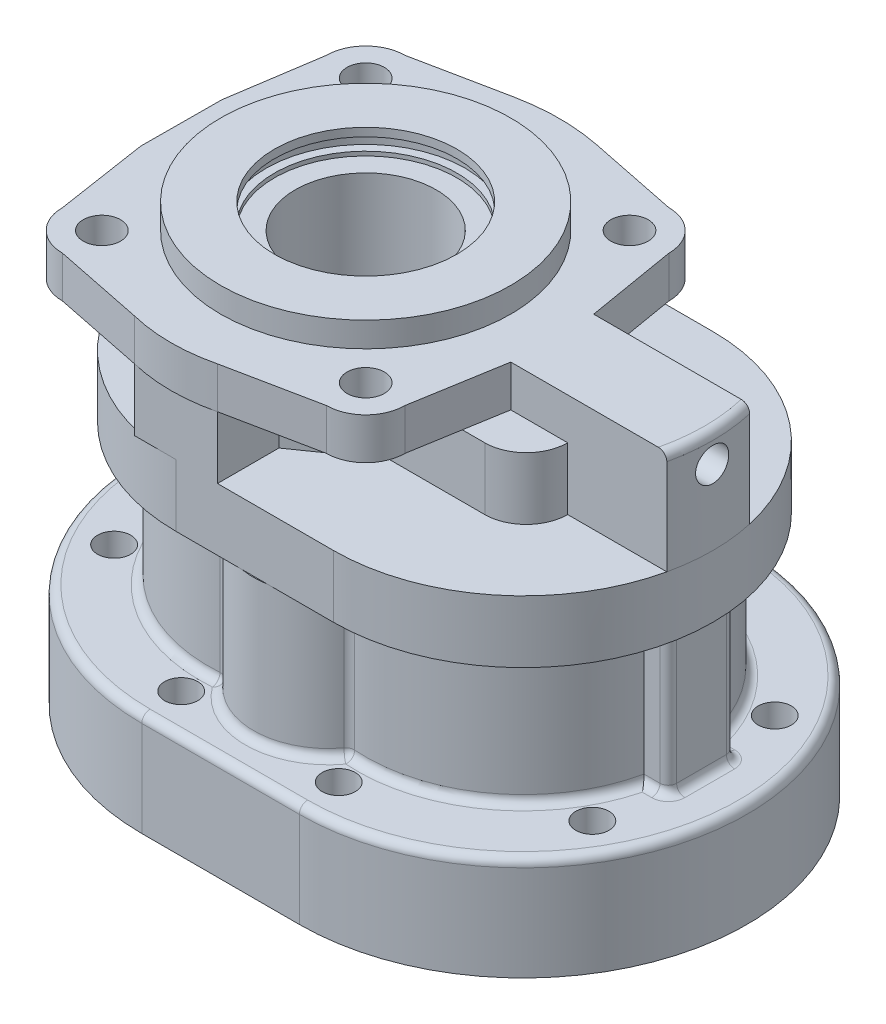
SolidWorks part; units mm, degrees
material "1.4000 (X6Cr13)"
ref_plane "Спереди" through (0, 0, 0) normal (0, 0, 1) x (1, 0, 0)
ref_plane "Сверху" through (0, 0, 0) normal (0, 1, 0) x (1, 0, 0)
ref_plane "Справа" through (0, 0, 0) normal (1, 0, 0) x (0, 0, -1)
sketch "Эскиз2" plane through (0, 0, 0) normal (0, 1, 0) x (1, 0, 0)
  line L0 (-87.7274, 0) -> (85.7597, 0) construction
  line L1 (6.0246, 54) -> (-31.9754, 54)
  line L2 (6.0246, -54) -> (-31.9754, -54)
  arc A3 (-31.9754, 54) -> (-31.9754, -54) centre (-31.9754, 0) ccw
  arc A4 (6.0246, -54) -> (6.0246, 54) centre (6.0246, 0) ccw
  dimension "D5" = 108
  dimension "D1" = 38
extrude "Вытянуть2" add sketch "Эскиз2" along normal blind 25
sketch "Эскиз4" plane through (0, 25, 0) normal (0, 1, 0) x (1, 0, 0)
  line L0 (91.9674, 0) -> (-114.468, 0) construction
  circle A8 centre (44.706, 22) radius 4
  circle A9 centre (44.706, -22) radius 4
  circle A10 centre (-70.6568, -22) radius 4
  circle A11 centre (-70.6568, 22) radius 4
  circle A12 centre (-31.9754, -44.5) radius 4
  circle A13 centre (6.0246, -44.5) radius 4
  circle A14 centre (6.0246, 44.5) radius 4
  circle A15 centre (-31.9754, 44.5) radius 4
  dimension "D6" = 8
  dimension "D7" = 8
  dimension "D8" = 8
  dimension "D9" = 8
  dimension "D10" = 8
  dimension "D11" = 8
  dimension "D12" = 8
  dimension "D13" = 8
extrude "Вырез-Вытянуть2" cut sketch "Эскиз4" against normal through all
sketch "Эскиз5" plane through (0, 25, 0) normal (0, 1, 0) x (1, 0, 0)
  line L0 (70.9678, 0) -> (-102.4067, 0) construction
  line L1 (6.0246, 38) -> (2.0064, 38)
  line L2 (-31.9754, -38) -> (-27.9572, -38)
  line L3 (2.0064, -38) -> (6.0246, -38)
  line L4 (-27.9572, 38) -> (-31.9754, 38)
  line L5 (-69.9754, 0) -> (-80.9754, 0)
  line L6 (44.0246, 0) -> (55.0246, 0)
  arc A1 (-28.0881, 37.8006) -> (-28.0881, -37.8006) centre (-31.9754, 0) ccw
  arc A2 (2.1373, 37.8006) -> (-28.0881, 37.8006) centre (-12.9754, 28.0227) ccw
  arc A3 (-26.574, -16.2296) -> (-27.6526, -17.6025) centre (-12.9754, -28.0227) ccw
  arc A4 (-28.0881, -37.8006) -> (2.1373, -37.8006) centre (-12.9754, -28.0227) ccw
  arc A5 (0.6232, 16.2296) -> (1.7018, 17.6025) centre (-12.9754, 28.0227) ccw
  arc A7 (2.1373, -37.8006) -> (2.1373, 37.8006) centre (6.0246, 0) ccw
  dimension "D1" = 76
  dimension "D3" = 36
extrude "Вытянуть5" add sketch "Эскиз5" along normal blind 34 contours L0 A7 A2 A1 | A7 L0 A1 A4 region at (-12.9754, 25, 18.2894) region at (-12.9754, 25, -18.2894)
sketch "Эскиз7" plane through (0, 25, 0) normal (0, 1, 0) x (1, 0, 0)
  line L1 (33.7864, 8) -> (33.7864, -8)
  line L3 (49.0246, 8) -> (49.0246, -8)
  line L4 (-12.9754, 63.0794) -> (-12.9754, -64.61) construction
  line L5 (49.0246, 8) -> (33.7864, 8)
  line L6 (49.0246, -8) -> (33.7864, -8)
  line L9 (-59.7372, 8) -> (-59.7372, -8)
  line L10 (6.0246, 0) -> (-93.5345, 0) construction
  line L11 (-74.9754, -8) -> (-59.7372, -8)
  line L12 (-74.9754, 8) -> (-74.9754, -8)
  line L13 (-74.9754, 8) -> (-59.7372, 8)
extrude "Вытянуть6" add sketch "Эскиз7" along normal blind 34
sketch "Эскиз9" plane through (0, 59, 0) normal (0, 1, 0) x (1, 0, 0)
  line L0 (77.4288, 0) -> (-110.5641, 0) construction
  line L1 (-110.5641, 0) -> (-110.2647, -0.7484) construction
  line L2 (-12.9754, 54) -> (-12.9754, 79.7772) construction
  line L3 (6.0246, 54) -> (-31.9754, 54) construction
  line L4 (-12.9754, 79.7772) -> (-12.9754, 45.75) construction
  line L5 (6.0246, 45.75) -> (-31.9754, 45.75)
  line L6 (6.0246, -45.75) -> (-31.9754, -45.75)
  line L7 (-12.9754, -45.75) -> (-12.9754, -73.7902) construction
  arc A0 (6.0246, -45.75) -> (6.0246, 45.75) centre (6.0246, 0) ccw
  arc A1 (-31.9754, 45.75) -> (-31.9754, -45.75) centre (-31.9754, 0) ccw
  dimension "D1" = 91.5
  dimension "D2" = 91.5
extrude "Вытянуть8" add sketch "Эскиз9" along normal blind 15
sketch "Эскиз10" plane through (0, 74, 0) normal (0, 1, 0) x (1, 0, 0)
  line L0 (73.3377, 0) -> (-104.2777, 0) construction
  line L1 (-31.9754, 59.8254) -> (-31.9754, -62.6925) construction
  line L2 (-21.9754, 45.75) -> (-41.9754, 45.75)
  line L3 (6.0246, 45.75) -> (-31.9754, 45.75) construction
  line L4 (-21.9754, 45.75) -> (-21.9754, 30.9233)
  line L5 (-31.9754, -45.75) -> (6.0246, -45.75) construction
  line L6 (-21.9754, -45.75) -> (-41.9754, -45.75)
  line L7 (-41.9754, 45.75) -> (-41.9754, 30.9233)
  line L8 (-76.6191, 10) -> (-76.6191, -10)
  line L9 (-76.6191, -10) -> (-62.8987, -10)
  line L10 (26.7556, 20) -> (26.7556, -20)
  line L11 (26.7556, 20) -> (-6.358, 20)
  line L12 (-6.358, 20) -> (-21.9754, 30.9233)
  line L13 (-41.9754, -30.9233) -> (-41.9754, -45.75)
  line L14 (-62.8987, 10) -> (-76.6191, 10)
  line L15 (-6.358, -20) -> (26.7556, -20)
  line L16 (-21.9754, -30.9233) -> (-21.9754, -45.75)
  line L17 (-6.358, -20) -> (-21.9754, -30.9233)
  arc A0 (-41.9754, 30.9233) -> (-62.8987, 10) centre (-31.9754, 0) ccw
  arc A1 (-31.9754, 45.75) -> (-31.9754, -45.75) centre (-31.9754, 0) ccw construction
  arc A3 (-62.8987, -10) -> (-41.9754, -30.9233) centre (-31.9754, 0) ccw
  point P19 (-31.9754, 45.75)
  point P20 (-31.9754, -45.75)
  point P29 (26.7556, 0)
  dimension "D1" = 65
  dimension "D2" = 20
extrude "Вытянуть12" add sketch "Эскиз10" along normal blind 15
sketch "Эскиз11" plane through (0, 89, 0) normal (0, 1, 0) x (1, 0, 0)
  line L0 (-91.5552, 0) -> (46.0634, 0) construction
  line L2 (-31.9754, -57.3023) -> (-31.9754, 59.4606) construction
  line L3 (13.0246, -10) -> (13.0246, 10)
  line L4 (13.0246, 10) -> (9.3444, 31.8198)
  line L5 (-0.1556, 41.3198) -> (-21.9754, 45.75)
  line L6 (-41.9754, 45.75) -> (-63.7952, 41.3198)
  line L7 (-73.2952, 31.8198) -> (-76.6191, 10)
  line L8 (-76.6191, 10) -> (-76.7193, -9.5419)
  line L9 (-76.7193, -9.5419) -> (-73.2952, -31.8198)
  line L10 (13.0246, -10) -> (9.3444, -31.8198)
  line L11 (-0.1556, -41.3198) -> (-21.9754, -45.75)
  line L12 (-63.7952, -41.3198) -> (-41.9754, -45.75)
  arc A1 (9.3444, 31.8198) -> (-0.1556, 41.3198) centre (-0.1556, 31.8198) ccw
  arc A2 (-21.9754, 45.75) -> (-41.9754, 45.75) centre (-31.9754, -3.5025) ccw
  arc A3 (-73.2952, 31.8198) -> (-63.7952, 41.3198) centre (-63.7952, 31.8198) cw
  arc A4 (-73.2952, -31.8198) -> (-63.7952, -41.3198) centre (-63.7952, -31.8198) ccw
  arc A5 (9.3444, -31.8198) -> (-0.1556, -41.3198) centre (-0.1556, -31.8198) cw
  arc A6 (-76.6191, 10) -> (-76.6191, -10) centre (-31.9754, 0) ccw construction
  arc A7 (-41.9754, -45.75) -> (-21.9754, -45.75) centre (-31.9754, -4.7961) ccw
  point P13 (13.0246, 0)
  dimension "D1" = 19
  dimension "D2" = 10
extrude "Вытянуть14" add sketch "Эскиз11" along normal blind 10
sketch "Эскиз12" plane through (0, 74, 0) normal (0, 1, 0) x (1, 0, 0)
  line L0 (19.9545, 0) -> (78.4595, 0) construction
  line L2 (50.6683, 10) -> (13.0246, 10)
  line L3 (13.0246, 10) -> (13.0246, -10)
  line L4 (13.0246, -10) -> (50.6683, -10)
  arc A0 (6.0246, -45.75) -> (6.0246, 45.75) centre (6.0246, 0) ccw construction
  arc A1 (50.6683, 10) -> (50.6683, -10) centre (6.3738, 0) cw
  point P9 (50.6683, 0)
  dimension "D1" = 10
extrude "Вытянуть15" add sketch "Эскиз12" along normal blind 25
fillet "Скругление12" radius 10 1 edges at (26.7556, 81.5, 20)
fillet "Скругление13" radius 10 1 edges at (26.7556, 81.5, -20)
sketch "Эскиз13" plane through (0, 0, 0) normal (0, -1, 0) x (1, 0, 0)
  line L0 (66.2281, 0) -> (-91.7631, 0) construction
  circle A0 centre (6.0246, 0) radius 22
extrude "Вырез-Вытянуть5" cut sketch "Эскиз13" against normal blind 68
sketch "Эскиз14" plane through (0, 68, 0) normal (0, -1, 0) x (1, 0, 0)
  circle A0 centre (6.0246, 0) radius 11.5
  dimension "D1" = 23
extrude "Вырез-Вытянуть6" cut sketch "Эскиз14" against normal blind 10
sketch "Эскиз15" plane through (0, 0, 0) normal (0, -1, 0) x (1, 0, 0)
  line L0 (68.4793, 0) -> (-98.8794, 0) construction
  circle A0 centre (-31.9754, 0) radius 22
  dimension "D1" = 44
extrude "Вырез-Вытянуть7" cut sketch "Эскиз15" against normal blind 68
sketch "Эскиз16" plane through (0, 68, 0) normal (0, -1, 0) x (1, 0, 0)
  circle A0 centre (-31.9754, 0) radius 16
  dimension "D1" = 32
extrude "Вырез-Вытянуть8" cut sketch "Эскиз16" against normal blind 4
sketch "Эскиз17" plane through (0, 72, 0) normal (0, -1, 0) x (1, 0, 0)
  circle A0 centre (-31.9754, 0) radius 14
  dimension "D1" = 28
extrude "Вырез-Вытянуть9" cut sketch "Эскиз17" against normal through all
sketch "Эскиз18" plane through (0, 99, 0) normal (0, 1, 0) x (1, 0, 0)
  circle A0 centre (-31.9754, 0) radius 35
  circle A1 centre (-31.9754, 0) radius 22
  dimension "D1" = 70
  dimension "D2" = 44
extrude "Вытянуть17" add sketch "Эскиз18" along normal blind 6
sketch "Эскиз19" plane through (0, 99, 0) normal (0, 1, 0) x (1, 0, 0)
  circle A0 centre (-31.9754, 0) radius 17
  dimension "D1" = 34
extrude "Вырез-Вытянуть11" cut sketch "Эскиз19" against normal blind 24
sketch "Эскиз20" plane through (0, 99, 0) normal (0, 1, 0) x (1, 0, 0)
  line L0 (-93.2842, 0) -> (42.4152, 0) construction
  line L1 (-31.9754, 67.5073) -> (-31.9754, -59.5354) construction
  circle A0 centre (-63.7952, 31.8198) radius 4.5
  circle A1 centre (-63.7952, -31.8198) radius 4.5
  circle A2 centre (-0.1556, -31.8198) radius 4.5
  circle A3 centre (-0.1556, 31.8198) radius 4.5
  dimension "D1" = 9
extrude "Вырез-Вытянуть12" cut sketch "Эскиз20" against normal blind 20
fillet "Скругление14" radius 2 1 edges at (51.7831, 99, 0)
sketch "Эскиз23" plane through (0, 0, 0) normal (1, 0, 0) x (0, 0, -1)
  line L0 (0, 122.2075) -> (0, -14.1985) construction
  line L1 (10, 97) -> (-10, 97) construction
  circle A0 centre (0, 92) radius 4
  dimension "D1" = 8
  dimension "D2" = 5
extrude "Вырез-Вытянуть13" cut sketch "Эскиз23" against normal blind 10 and the other way through all
sketch "Эскиз24" plane through (0, 0, 0) normal (1, 0, 0) x (0, 0, -1)
  line L0 (0, 107.6828) -> (0, 50.503) construction
  circle A0 centre (0, 92) radius 1
  dimension "D1" = 2
extrude "Вырез-Вытянуть14" cut sketch "Эскиз24" against normal blind 25
sketch "Эскиз21" plane through (0, 0, 0) normal (0, 0, 1) x (1, 0, 0)
  line L0 (-31.9754, 125.4433) -> (-31.9754, -15.7169) construction
  line L1 (-10.6116, 103) -> (-7.9754, 103)
  line L2 (-7.9754, 103) -> (-7.9754, 100)
  line L3 (-7.9754, 100) -> (-10.6116, 100)
  line L4 (-10.6116, 100) -> (-10.6116, 103)
  line L5 (3.0246, 105) -> (-66.9754, 105) construction
  dimension "D1" = 3
  dimension "D2" = 2
  dimension "D3" = 2
revolve "Вырез-Повернуть2" cut sketch "Эскиз21" angle 360 about L0
sketch "Эскиз25" plane through (0, 0, 0) normal (0, -1, 0) x (1, 0, 0)
  line L0 (-12.9754, 60.9181) -> (-12.9754, -69.0006) construction
  line L1 (-31.9754, 54) -> (6.0246, 54) construction
  circle A0 centre (-12.9754, 28) radius 9
  dimension "D1" = 18
  dimension "D2" = 26
extrude "Вырез-Вытянуть15" cut sketch "Эскиз25" against normal blind 55
sketch "Эскиз26" plane through (0, 0, 0) normal (0, -1, 0) x (1, 0, 0)
  line L0 (-12.9754, -54) -> (-12.9754, 66.7038) construction
  line L1 (6.0246, -54) -> (-31.9754, -54) construction
  circle A0 centre (-12.9754, -26.5) radius 5.5
  dimension "D1" = 11
  dimension "D2" = 27.5
extrude "Вырез-Вытянуть16" cut sketch "Эскиз26" against normal blind 67
sketch "Эскиз27" plane through (0, 0, 0) normal (0, 0, 1) x (1, 0, 0)
  line L1 (-9.4267, 22.8961) -> (14.8327, 22.8961)
  line L2 (-9.4267, 22.8961) -> (-9.4267, 41.2525)
  line L3 (-9.4267, 41.2525) -> (14.8327, 41.2525)
  line L4 (14.8327, 22.8961) -> (14.8327, 41.2525)
sketch "Эскиз28" plane through (0, 0, 0) normal (0, -1, 0) x (1, 0, 0)
  circle A0 centre (-12.9206, 0) radius 32.2869
sweep "Вырез-По траектории1" cut profiles "Эскиз27" path "Эскиз28"
fillet "Скругление2" radius 2 2 edges at (49.0246, 42, -8) (49.0246, 42, 8)
fillet "Скругление3" radius 2 15 edges at (45.0988, 25, 8) (48.4388, 25, 7.4142) (49.0246, 25, 0) (48.4388, 25, -7.4142) (45.0988, 25, -8) (-54.3046, 25, -30.7475) (-12.9754, 25, -46.0227) (28.3538, 25, -30.7475) (28.3538, 25, 30.7475) (-54.3046, 25, 30.7475) (-12.9754, 25, 46.0227) (2.1373, 42, 37.8006) (-28.0881, 42, 37.8006) (-28.0881, 42, -37.8006) (2.1373, 42, -37.8006)
fillet "Скругление4" radius 2 4 edges at (-12.9754, 25, -54) (-85.9754, 25, 0) (60.0246, 25, 0) (-12.9754, 25, 54)
sketch "Эскиз8" plane through (0, 59, 0) normal (0, 1, 0) x (1, 0, 0)
  line L0 (80.5582, 0) -> (-110.8569, 0) construction
  line L1 (6.0246, 45.5) -> (-31.9754, 45.5)
  line L2 (6.0246, -45.5) -> (-31.9754, -45.5)
  arc A0 (6.0246, -45.5) -> (6.0246, 45.5) centre (6.0246, 0) ccw
  arc A1 (-31.9754, 45.5) -> (-31.9754, -45.5) centre (-31.9754, 0) ccw
  dimension "D1" = 91
  dimension "D2" = 91
extrude "Вытянуть7" add sketch "Эскиз8" along normal blind 15
